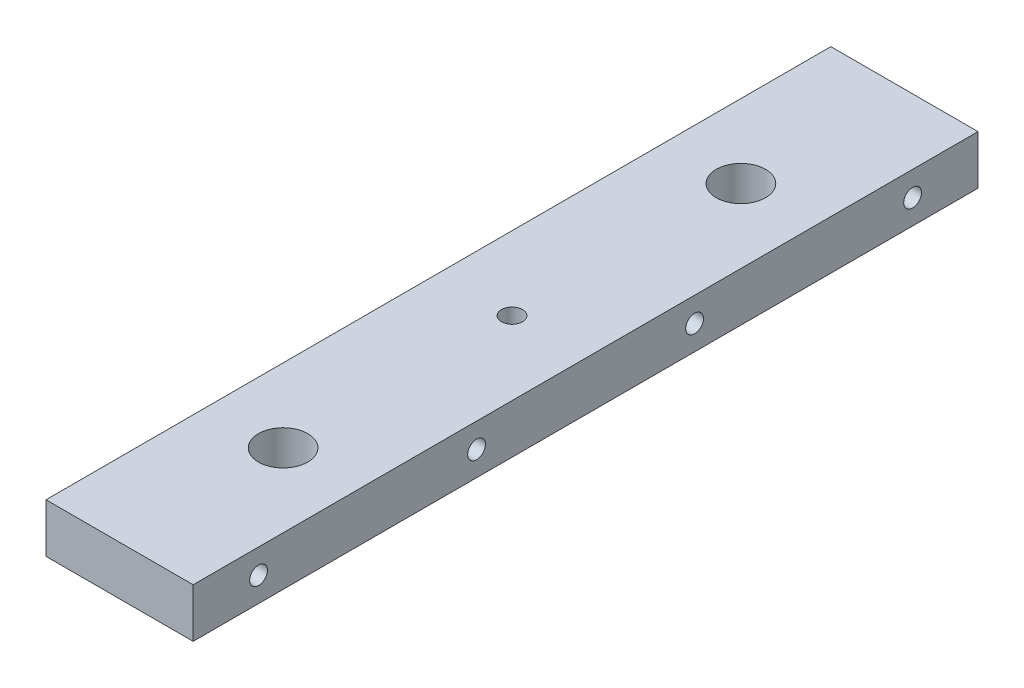
SolidWorks part; units mm, degrees
ref_plane "Front Plane" through (0, 0, 0) normal (0, 0, 1) x (1, 0, 0)
ref_plane "Top Plane" through (0, 0, 0) normal (0, 1, 0) x (1, 0, 0)
ref_plane "Right Plane" through (0, 0, 0) normal (1, 0, 0) x (0, 0, -1)
sketch "Sketch2" plane through (0, 0, 0) normal (0, 1, 0) x (1, 0, 0)
  line L0 (0, 0) -> (0, 152.4)
  line L1 (0, 152.4) -> (28.575, 152.4)
  line L2 (28.575, 152.4) -> (28.575, 0)
  line L3 (28.575, 0) -> (0, 0)
  dimension "D1" = 152.4
  dimension "D2" = 28.575
extrude "Boss-Extrude1" add sketch "Sketch2" along normal blind 9.525
sketch "Sketch3" plane through (0, 0, 0) normal (-1, 0, 0) x (0, 0, 1)
  line L3 (-152.4, 9.525) -> (0, 9.525) construction
  line L4 (-152.4, 9.525) -> (-152.4, 0) construction
  point P6 (-139.7, 4.7625)
  point P14 (-139.7, 4.7625)
  dimension "D1" = 4.7625
  dimension "D2" = 12.7
sketch "Sketch8" plane through (0, 0, 0) normal (-1, 0, 0) x (0, 0, 1)
  point P0 (-139.7, 4.7625)
hole_wizard "#5 Clearance Hole3" positions "Sketch8" profile "Sketch9" hole size "#5" standard "ANSI Inch"
sketch "Sketch9" plane through (0, 4.7625, -139.7) normal (0, 1, 0) x (0, 0, 1)
  line L0 (0, 0) -> (0, 13.7378)
  line L1 (0, 13.7378) -> (1.7272, 12.7)
  line L2 (1.7272, 12.7) -> (1.7272, 0)
  line L5 (1.7272, 0) -> (0, 0)
  line L10 (0, 13.7378) -> (-1.7272, 12.7) construction
  line L11 (0, -6.35) -> (0, 107.95) construction
  dimension "Hole Dia." = 3.4544
  dimension "Hole Depth" = 12.7
  dimension "Drill Angle" = 118
pattern_linear "LPattern1" count 4 spacing 42.3333 along (0, 0, 1) skipping (2, 0) of "#5 Clearance Hole3"
sketch "Sketch10" plane through (28.575, 0, 0) normal (1, 0, 0) x (0, 0, -1)
  line L0 (0, 9.525) -> (0, 0) construction
  line L1 (0, 9.525) -> (152.4, 9.525) construction
  point P0 (12.7, 4.7625)
  point P1 (12.7, 4.7625)
  point P5 (0, 4.7625)
  point P9 (12.7, 4.7625)
  dimension "D1" = 12.7
  dimension "D2" = 4.7625
hole_wizard "#5 Clearance Hole4" positions "Sketch10" profile "Sketch11" hole size "#5" standard "ANSI Inch"
sketch "Sketch11" plane through (28.575, 4.7625, -12.7) normal (0, 1, 0) x (0, 0, -1)
  line L0 (0, 0) -> (0, 13.7378)
  line L1 (0, 13.7378) -> (1.7272, 12.7)
  line L2 (1.7272, 12.7) -> (1.7272, 0)
  line L5 (1.7272, 0) -> (0, 0)
  line L10 (0, 13.7378) -> (-1.7272, 12.7) construction
  line L11 (0, -6.35) -> (0, 107.95) construction
  dimension "Hole Dia." = 3.4544
  dimension "Hole Depth" = 12.7
  dimension "Drill Angle" = 118
pattern_linear "LPattern2" count 4 spacing 42.3333 along (0, 0, -1) of "#5 Clearance Hole4"
sketch "Sketch12" plane through (0, 9.525, 0) normal (0, 1, 0) x (1, 0, 0)
  line L0 (28.575, 0) -> (28.575, 152.4) construction
  line L2 (0, 0) -> (28.575, 0) construction
  circle A0 centre (14.2875, 76.2) radius 2.05
  circle A1 centre (14.2875, 31.75) radius 4.7879
  circle A2 centre (14.2875, 120.65) radius 4.7879
  point P0 (14.2875, 120.65)
  point P1 (14.2875, 76.2)
  point P2 (14.2875, 31.75)
  dimension "D7" = 4.1
  dimension "D8" = 9.5758
  dimension "D9" = 9.5758
  dimension "D1" = 14.2875
  dimension "D2" = 14.2875
  dimension "D3" = 14.2875
  dimension "D4" = 76.2
  dimension "D5" = 44.45
  dimension "D6" = 44.45
extrude "Cut-Extrude1" cut sketch "Sketch12" against normal through all
sketch "Sketch13" plane through (0, 0, 0) normal (-1, 0, 0) x (0, 0, 1)
  line L0 (-152.4, 9.525) -> (0, 9.525) construction
  line L1 (0, 9.525) -> (0, 0) construction
  point P0 (-38.1, 4.7625)
  point P5 (-69.85, 4.7625)
  dimension "D1" = 4.7625
  dimension "D2" = 38.1
  dimension "D3" = 31.75
hole_wizard "#5 Clearance Hole5" positions "Sketch13" profile "Sketch14" hole size "#5" standard "ANSI Inch"
sketch "Sketch14" plane through (0, 4.7625, -38.1) normal (0, 1, 0) x (0, 0, 1)
  line L0 (0, 0) -> (0, 13.7378)
  line L1 (0, 13.7378) -> (1.7272, 12.7)
  line L2 (1.7272, 12.7) -> (1.7272, 0)
  line L5 (1.7272, 0) -> (0, 0)
  line L10 (0, 13.7378) -> (-1.7272, 12.7) construction
  line L11 (0, -6.35) -> (0, 107.95) construction
  dimension "Hole Dia." = 3.4544
  dimension "Hole Depth" = 12.7
  dimension "Drill Angle" = 118
